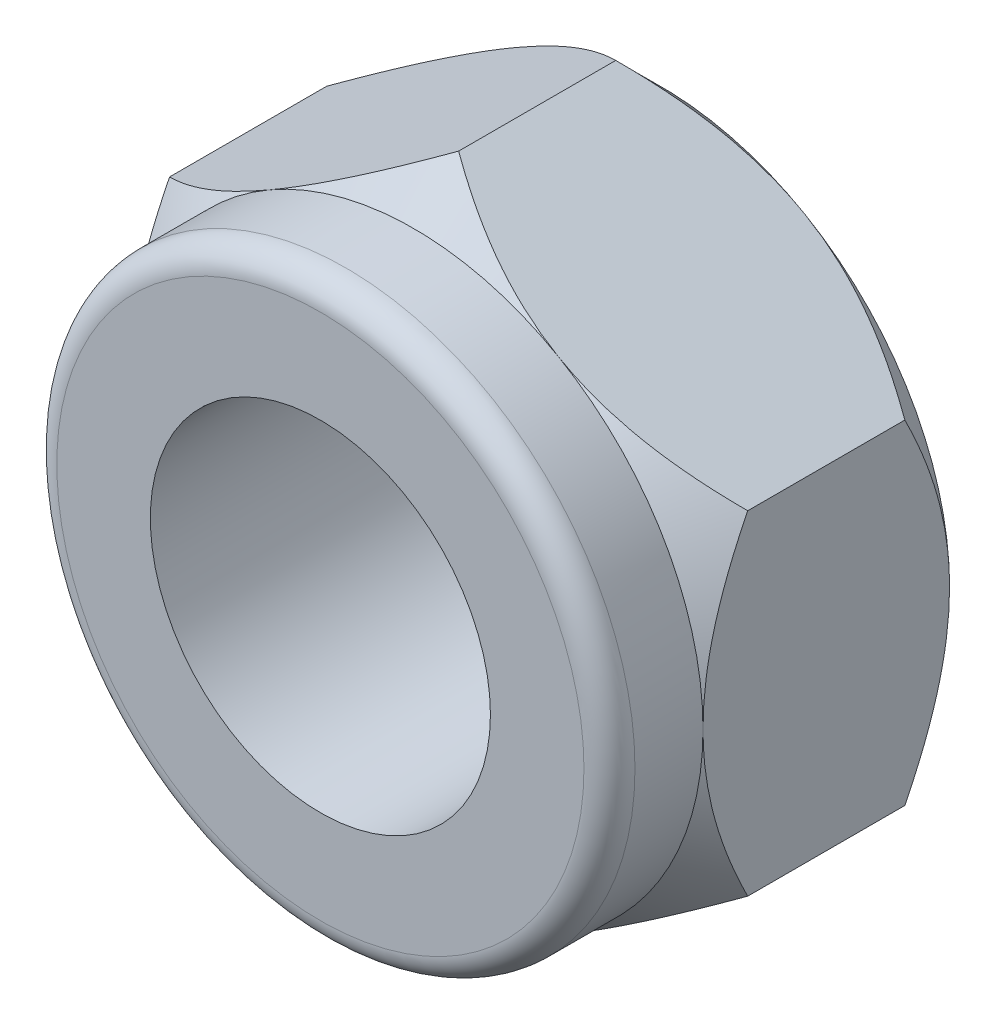
SolidWorks part; units mm, degrees
material "AISI 304"
ref_plane "前视基准面" through (0, 0, 0) normal (0, 0, 1) x (1, 0, 0)
ref_plane "上视基准面" through (0, 0, 0) normal (0, 1, 0) x (1, 0, 0)
ref_plane "右视基准面" through (0, 0, 0) normal (1, 0, 0) x (0, 0, -1)
sketch "草图1" plane through (0, 0, 0) normal (0, 0, 1) x (1, 0, 0)
  line L1 (0, 3.926) -> (-3.4, 1.963)
  line L2 (-3.4, 1.963) -> (-3.4, -1.963)
  line L3 (-3.4, -1.963) -> (0, -3.926)
  line L4 (0, -3.926) -> (3.4, -1.963)
  line L5 (3.4, -1.963) -> (3.4, 1.963)
  line L6 (3.4, 1.963) -> (0, 3.926)
  circle A0 centre (0, 0) radius 3.4 construction
  dimension "D1" = 6.8
extrude "凸台-拉伸1" add sketch "草图1" along normal blind 2.9
sketch "草图2" plane through (0, 0, 2.9) normal (0, 0, 1) x (1, 0, 0)
  circle A0 centre (0, 0) radius 3.4
extrude "凸台-拉伸2" add sketch "草图2" along normal blind 1.1
sketch "草图3" plane through (0, 0, 4) normal (0, 0, 1) x (1, 0, 0)
  circle A0 centre (0, 0) radius 2
  dimension "D1" = 4
extrude "切除-拉伸1" cut sketch "草图3" against normal through all
extrude "切除-拉伸2" cut sketch "草图2<2>" against normal blind 1.1 draft 45 flip side to cut
sketch "草图2<2>" plane through (0, 0, 2.9) normal (0, 0, 1) x (1, 0, 0) same geometry as "草图2"
sketch "草图4" plane through (0, 0, 0) normal (0, 0, -1) x (-1, 0, 0)
  circle A0 centre (0, 0) radius 3.4
extrude "切除-拉伸3" cut sketch "草图4" against normal blind 1.1 draft 45 flip side to cut
fillet "圆角1" radius 0.3 1 edges at (3.4, 0, 4)
